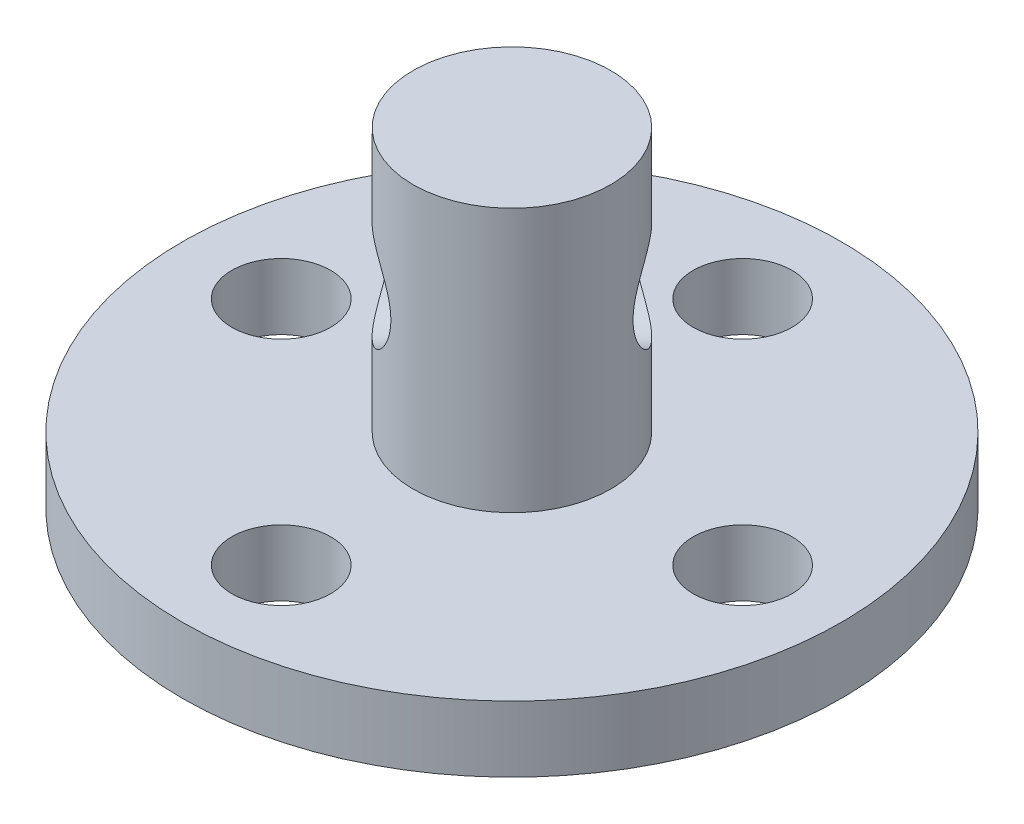
SolidWorks part; units mm, degrees
ref_plane "前视基准面" through (0, 0, 0) normal (0, 0, 1) x (1, 0, 0)
ref_plane "上视基准面" through (0, 0, 0) normal (0, 1, 0) x (1, 0, 0)
ref_plane "右视基准面" through (0, 0, 0) normal (1, 0, 0) x (0, 0, -1)
sketch "草图1" plane through (0, 0, 0) normal (0, 1, 0) x (1, 0, 0)
  line L0 (0, 0) -> (0, 7) construction
  circle A0 centre (0, 0) radius 10
  circle A1 centre (0, 0) radius 3
  circle A2 centre (0, 7) radius 1.5
  circle A3 centre (7, 0) radius 1.5
  circle A4 centre (0, -7) radius 1.5
  circle A5 centre (-7, 0) radius 1.5
  dimension "D1" = 4
extrude "凸台-拉伸1" add sketch "草图1" along normal blind 2
sketch "草图2" plane through (0, 0, 0) normal (0, 1, 0) x (1, 0, 0)
  circle A0 centre (0, 0) radius 3
extrude "凸台-拉伸2" add sketch "草图2" along normal blind 10
sketch "草图3" plane through (0, 0, 0) normal (0, 0, 1) x (1, 0, 0)
  line L0 (0, 0) -> (0, 12.3304) construction
ref_axis "基准轴1" through (0, 0, 0) along (0, 1, 0)
ref_plane "基准面1" through (0, 0, 0) normal (0.7071, 0, -0.7071) x (0, 1, 0)
sketch "草图5" plane through (0, 0, 0) normal (0.7071, 0, -0.7071) x (0, 1, 0)
  line L0 (10, 0) -> (6, 0) construction
  line L1 (10, -3) -> (10, 3) construction
  line L2 (0, 0) -> (12.3304, 0) construction
  circle A0 centre (6, 0) radius 1.5
extrude "切除-拉伸3" cut sketch "草图5" against normal mid plane 10
